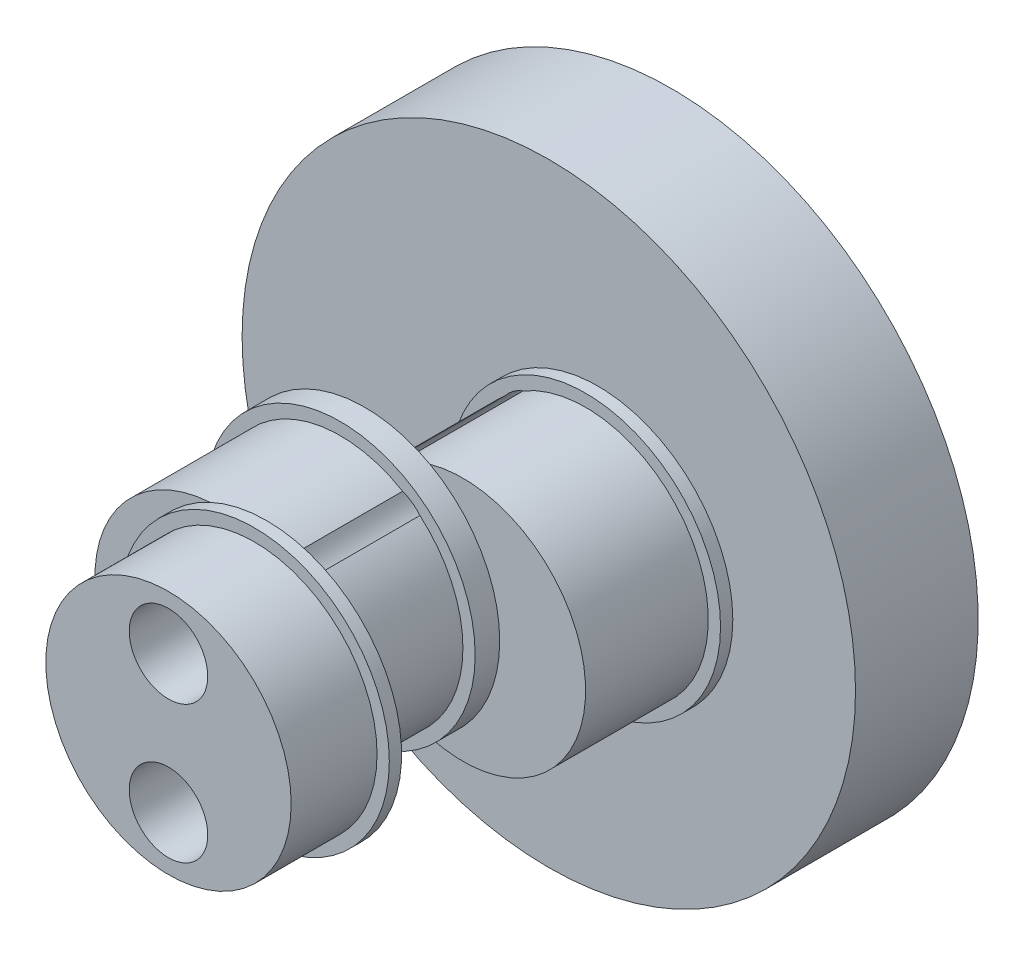
SolidWorks part; units mm, degrees
ref_plane "Front Plane" through (0, 0, 0) normal (0, 0, 1) x (1, 0, 0)
ref_plane "Top Plane" through (0, 0, 0) normal (0, 1, 0) x (1, 0, 0)
ref_plane "Right Plane" through (0, 0, 0) normal (1, 0, 0) x (0, 0, -1)
sketch "Sketch1" plane through (0, 0, -2) normal (0, 0, -1) x (-1, 0, 0)
  circle A0 centre (0, 0) radius 12.5
  dimension "D1" = 25
extrude "Boss-Extrude1" add sketch "Sketch1" against normal up to surface (5 mm away) contours A0
sketch "Sketch2" plane through (0, 0, 3) normal (0, 0, 1) x (1, 0, 0)
  line L0 (0, 0) -> (2, 0)
  circle A0 centre (2, 0) radius 5
  circle A1 centre (2, 0) radius 5.4995
  dimension "D2" = 10
extrude "Boss-Extrude2" add sketch "Sketch2" along normal blind 0.5 contours A1 A0 region at (-3.3439, 0, 3)
extrude "Boss-Extrude3" add sketch "Sketch2<3>" along normal blind 5.5 contours A0 region at (-2.8586, 0, 3)
sketch "Sketch2<3>" plane through (0, 0, 3) normal (0, 0, 1) x (1, 0, 0) same geometry as "Sketch2"
sketch "Sketch3" plane through (0, 0, 3) normal (0, 0, 1) x (1, 0, 0)
  line L0 (0, 0) -> (-2, 0)
  circle A0 centre (-2, 0) radius 5
  circle A1 centre (-2, 0) radius 5.5
  circle M1 centre (2, 0) radius 5.4995
  dimension "D2" = 10
  dimension "D3" = 11
extrude "Boss-Extrude4" add sketch "Sketch3" along normal blind 1 from surface contours A1 A0 M1 | A1 A0 M1 region at (2.0707, 3.0899, 3) region at (-7.1331, 0, 3) starting at face at (7, 0, 8.5)
extrude "Boss-Extrude5" add sketch "Sketch3<3>" along normal blind 6 from surface contours A0 M1 | A0 region at (1.8901, -2.9528, 3) region at (-4.3558, 0, 3) starting at face at (7, 0, 8.5)
sketch "Sketch3<3>" plane through (0, 0, 3) normal (0, 0, 1) x (1, 0, 0) same geometry as "Sketch3"
sketch "Sketch4" plane through (0, 0, 3) normal (0, 0, 1) x (1, 0, 0)
  circle A0 centre (0, 0) radius 5
  circle A1 centre (0, 0) radius 5.5
  dimension "D1" = 10
  dimension "D2" = 11
extrude "Boss-Extrude6" add sketch "Sketch4" along normal blind 0.5 from surface starting at face at (3, 0, 14.5)
extrude "Boss-Extrude7" add sketch "Sketch4<7>" along normal blind 4 from surface contours A0 starting at face at (-6.25, 0, 14.5)
sketch "Sketch4<7>" plane through (0, 0, 3) normal (0, 0, 1) x (1, 0, 0) same geometry as "Sketch4"
sketch "Sketch5" plane through (0, 0, 18.5) normal (0, 0, 1) x (1, 0, 0)
  line L1 (0, 2.8) -> (0, 0) construction
  line L2 (0, 0) -> (0, -2.8) construction
  circle A0 centre (0, 2.8) radius 1.6
  circle A1 centre (0, -2.8) radius 1.6
  dimension "D3" = 3.2
  dimension "D4" = 3.2
  dimension "D1" = 2.8
  dimension "D2" = 2.8
extrude "Cut-Extrude1" cut sketch "Sketch5" against normal through all
equation "\"CenterShaft\"=25"
equation "\"D1@Sketch1\"=\"CenterShaft\""
equation "\"Eccentricity\"=2"
equation "\"D1@Sketch2\"=\"Eccentricity\""
equation "\"CycCamShaft\"=10"
equation "\"D2@Sketch2\"=\"CycCamShaft\""
equation "\"D2@Sketch3\"=\"CycCamShaft\""
equation "\"D1@Sketch4\"=\"CycCamShaft\""
equation "\"RingPinShaft\"= 5"
equation "\"CenterBearingOut\"=32"
equation "\"RingPostIn\"=5"
equation "\"CamBearingOut\"=15.15"
equation "\"DiskOutputShaft\"=10"
